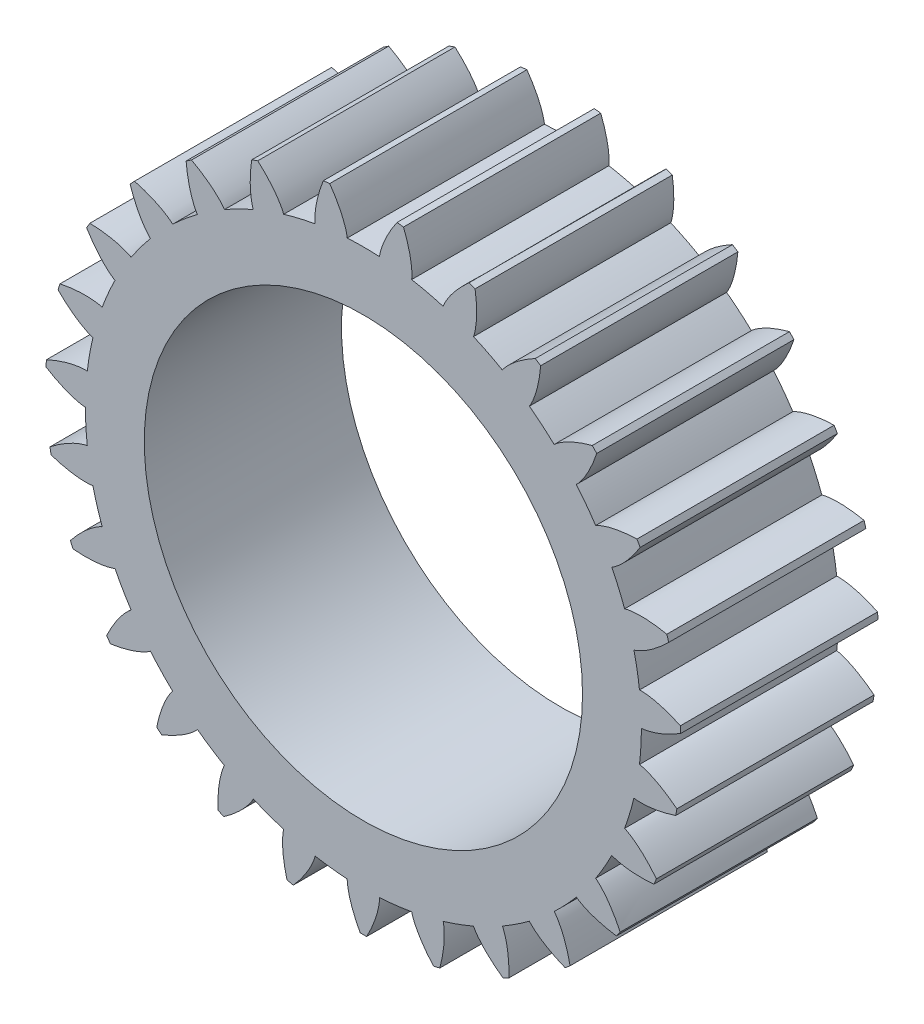
SolidWorks part; units mm, degrees
ref_plane "Front Plane" through (0, 0, 0) normal (0, 0, 1) x (1, 0, 0)
ref_plane "Top Plane" through (0, 0, 0) normal (0, 1, 0) x (1, 0, 0)
ref_plane "Right Plane" through (0, 0, 0) normal (1, 0, 0) x (0, 0, -1)
sketch "Sketch1" plane through (0, 0, 0) normal (0, 0, 1) x (1, 0, 0)
  line L0 (0, 0) -> (32.1677, -1.8736) construction
  line L1 (0, 0) -> (32.1677, 1.8736) construction
  line L2 (0, 0) -> (32.1677, -1.8736) construction
  line L3 (0, 0) -> (32.2222, 0) construction
  line L4 (0, 0) -> (31.7327, 5.5953) construction
  line L5 (22.1846, 1.2921) -> (32.1677, 1.8736)
  line L6 (22.1846, -1.2921) -> (28.1431, -1.6391)
  line L7 (28.1908, 0) -> (48.983, 0)
  circle A0 centre (0, 0) radius 30 construction
  circle A1 centre (0, 0) radius 27.2222 construction
  circle A2 centre (0, 0) radius 28.1908 construction
  circle A3 centre (0, 0) radius 32.2222 construction
  arc A4 (22.1846, 1.2921) -> (22.1846, -1.2921) centre (0, 0) cw
  arc A5 (28.1431, -1.6391) -> (28.1894, 0.2756) centre (0, 0) ccw
  arc A6 (32.1677, 1.8736) -> (32.1851, 1.5459) centre (0, 0) cw
  spline S0 degree 4 poles (28.1908, 0) (28.228, 0.0011) (28.3023, 0.0054) (28.5101, 0.0281) (28.9022, 0.0992) (29.4929, 0.2558) (30.2824, 0.5425) (31.2625, 0.9958) (32.3595, 1.6261) (33.5016, 2.4185) (34.6589, 3.37) (35.7436, 4.4033) (36.7568, 5.5064) (37.7467, 6.7274) (38.8771, 8.3118) (40.0789, 10.2986) (41.271, 12.7185) (42.3445, 15.5172) (43.1763, 18.3964) (43.776, 21.3325) (44.1527, 24.305) (44.3156, 27.2967) (44.2788, 29.9178) (44.1374, 31.9721) (43.9793, 33.4603) (43.8371, 34.5746) (43.6724, 35.6837) (43.4781, 36.7925) (43.2581, 37.889) (43.0537, 38.8085) (42.8844, 39.5249) (42.7108, 40.2082) (42.5637, 40.7635) (42.3873, 41.3944) (42.2694, 41.8019) (42.0732, 42.4584) (41.9123, 42.9664) (41.7131, 43.5823) (41.5269, 44.1284) (41.3218, 44.7155) (41.1191, 45.2701) (40.9566, 45.7041) (40.8499, 45.9799) (40.7944, 46.123) knots 0 0 0 0 0 0.002802 0.005604 0.015718 0.02996 0.048734 0.068727 0.096889 0.125051 0.153212 0.181374 0.209535 0.237696 0.271429 0.327752 0.384075 0.440398 0.496721 0.553044 0.609367 0.66569 0.722013 0.750174 0.764255 0.778336 0.806497 0.834659 0.84874 0.86282 0.876901 0.890982 0.900036 0.909091 0.920455 0.931818 0.943182 0.954545 0.965909 0.977273 0.988636 1 1 1 1 1 construction
  spline S1 degree 4 poles (28.1908, 0) (28.228, 0.0011) (28.3023, 0.0054) (28.5101, 0.0281) (28.9022, 0.0992) (29.4929, 0.2558) (30.2824, 0.5425) (31.2625, 0.9958) (32.3595, 1.6261) (33.5016, 2.4185) (34.6589, 3.37) (35.7436, 4.4033) (36.7568, 5.5064) (37.7467, 6.7274) (38.8771, 8.3118) (40.0789, 10.2986) (41.271, 12.7185) (42.3445, 15.5172) (43.1763, 18.3964) (43.776, 21.3325) (44.1527, 24.305) (44.3156, 27.2967) (44.2788, 29.9178) (44.1374, 31.9721) (43.9793, 33.4603) (43.8371, 34.5746) (43.6724, 35.6837) (43.4781, 36.7925) (43.2581, 37.889) (43.0537, 38.8085) (42.8844, 39.5249) (42.7108, 40.2082) (42.5637, 40.7635) (42.4333, 41.2298) (42.3729, 41.442) (42.3426, 41.5471) knots 0 0 0 0 0 0.002802 0.005604 0.015718 0.02996 0.048734 0.068727 0.096889 0.125051 0.153212 0.181374 0.209535 0.237696 0.271429 0.327752 0.384075 0.440398 0.496721 0.553044 0.609367 0.66569 0.722013 0.750174 0.764255 0.778336 0.806497 0.834659 0.84874 0.86282 0.876901 0.890982 0.900036 0.909091 0.909091 0.909091 0.909091 0.909091
  point P10 (27.1762, 1.5828)
  point P21 (27.2222, 0)
  dimension "pitchRadius" = 30
  dimension "addendumRadius" = 32.2222
  dimension "dedendumRadius" = 27.2222
  dimension "baseRadius" = 28.1908
  dimension "D1" = 6.667
  dimension "D2" = 3.333
  dimension "toothArc" = 13.333
  dimension "D3" = 5
extrude "Boss-Extrude1" add sketch "Sketch1" along normal blind 20 contours S1 A6 L5 | L7 S1 L5 A4 L6 region at (26.2487, 0.2285, 0)
mirror "Mirror1" about plane through (0, 0, 20) normal (-0.0581, 0.9983, 0) of "Boss-Extrude1"
pattern_circular "CirPattern1" count 27 over 360 about axis through (0, 0, 20) along (0, 0, -1) of "Boss-Extrude1", "Mirror1"
ref_axis "Axis1" through (0, 0, 0) along (0, 0, 1)
equation "\"D1@Sketch1\"=\"toothArc@Sketch1\"/2"
equation "\"D2@Sketch1\"=\"toothArc@Sketch1\"/4"
equation "\"pitchRadius\"= 3"
equation "\"nTeeth\"= 27"
equation "\"pressureAngle\"= 20"
equation "\"baseRadius\"= \"pitchRadius\" * cos ( \"pressureAngle\" )"
equation "\"diametralPitch\"= \"nTeeth\" / ( 2 * \"pitchRadius\" )'note units: cm^-1"
equation "\"dedendum\"= 1.25 / \"diametralPitch\"'for full depth, 20 deg pressure angle"
equation "\"addendum\"= 1 / \"diametralPitch\""
equation "\"pitchRadius@Sketch1\"= \"pitchRadius\""
equation "\"addendumRadius@Sketch1\"= \"pitchRadius\" + \"addendum\""
equation "\"dedendumRadius@Sketch1\"= \"pitchRadius\" - \"dedendum\""
equation "\"baseRadius@Sketch1\"= \"baseRadius\""
equation "\"toothArc@Sketch1\"=360/\"nTeeth\""
equation "\"D1@CirPattern1\"=\"nTeeth\""
